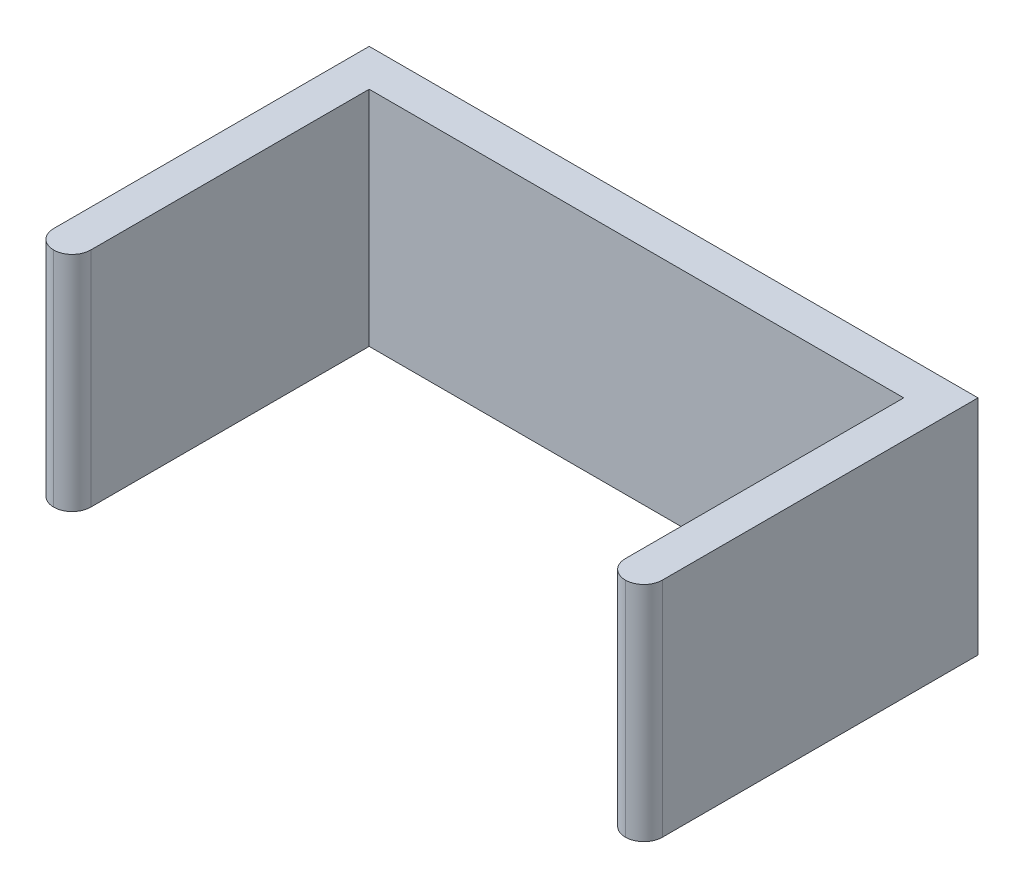
SolidWorks part; units mm, degrees
ref_plane "前基準面" through (0, 0, 0) normal (0, 0, 1) x (1, 0, 0)
ref_plane "上基準面" through (0, 0, 0) normal (0, 1, 0) x (1, 0, 0)
ref_plane "右基準面" through (0, 0, 0) normal (1, 0, 0) x (0, 0, -1)
sketch "草圖1" plane through (0, 0, 0) normal (0, 0, 1) x (1, 0, 0)
  line L1 (-32.4651, 19.8) -> (49.5349, 19.8)
  line L2 (-32.4651, 19.8) -> (-32.4651, -10.2)
  line L3 (-32.4651, -10.2) -> (49.5349, -10.2)
  line L4 (49.5349, 19.8) -> (49.5349, -10.2)
  dimension "D1" = 82
  dimension "D2" = 30
extrude "填料-伸長1" add sketch "草圖1" along normal blind 5
sketch "草圖2" plane through (0, 0, 5) normal (0, 0, 1) x (1, 0, 0)
  line L0 (-32.4651, -10.2) -> (49.5349, -10.2) construction
  line L1 (-32.4651, 19.8) -> (-27.4651, 19.8)
  line L2 (-32.4651, 19.8) -> (-32.4651, -10.2)
  line L3 (-32.4651, -10.2) -> (-27.4651, -10.2)
  line L4 (-27.4651, 19.8) -> (-27.4651, -10.2)
  line L6 (49.5349, 19.8) -> (44.5349, 19.8)
  line L7 (49.5349, 19.8) -> (49.5349, -10.2)
  line L8 (49.5349, -10.2) -> (44.5349, -10.2)
  line L9 (44.5349, 19.8) -> (44.5349, -10.2)
  dimension "D1" = 5
  dimension "D2" = 5
extrude "填料-伸長2" add sketch "草圖2" along normal blind 40
fillet "圓角1" radius 2.5 4 edges at (44.5349, 4.8, 45) (-27.4651, 4.8, 45) (49.5349, 4.8, 45) (-32.4651, 4.8, 45)
